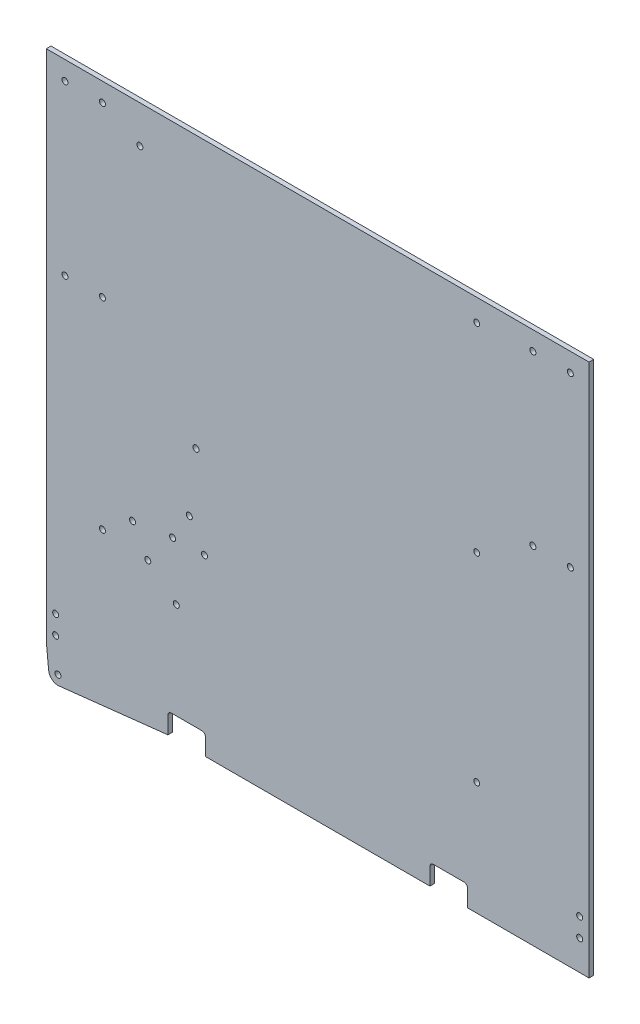
SolidWorks part; units mm, degrees
ref_plane "Front Plane" through (0, 0, 0) normal (0, 0, 1) x (1, 0, 0)
ref_plane "Top Plane" through (0, 0, 0) normal (0, 1, 0) x (1, 0, 0)
ref_plane "Right Plane" through (0, 0, 0) normal (1, 0, 0) x (0, 0, -1)
sketch "Sketch1" plane through (0, 0, 0) normal (0, 0, 1) x (1, 0, 0)
  line L0 (82.55, -20.32) -> (82.55, -6.35)
  line L2 (0, 0) -> (0, 341.63)
  line L3 (0, 341.63) -> (368.3, 341.63)
  line L4 (368.3, -20.32) -> (368.3, 341.63)
  line L5 (82.55, -6.35) -> (107.95, -6.35)
  line L6 (107.95, -6.35) -> (107.95, -20.32)
  line L7 (107.95, -20.32) -> (260.35, -20.32)
  line L8 (260.35, -20.32) -> (260.35, -6.35)
  line L9 (260.35, -6.35) -> (285.75, -6.35)
  line L10 (285.75, -6.35) -> (285.75, -20.32)
  line L11 (285.75, -20.32) -> (368.3, -20.32)
  line L12 (361.95, 12.7) -> (368.3, 12.7) construction
  line L13 (0, 0) -> (6.35, 0) construction
  line L14 (0.0315, -6.9818) -> (1.619, -22.8568)
  line L15 (8.6391, -28.5361) -> (82.55, -20.32)
  line L16 (0, 0) -> (0, -6.35)
  line L17 (85.725, 97.155) -> (82.9754, 95.5675) construction
  line L18 (97.0634, 115.6163) -> (58.5686, 93.3913) construction
  line L19 (97.0634, 115.6163) -> (107.3822, 97.7437) construction
  line L20 (58.5686, 93.3913) -> (68.8873, 75.5187) construction
  line L21 (107.3822, 97.7437) -> (68.8873, 75.5187) construction
  line L22 (97.0634, 115.6163) -> (68.8873, 75.5187) construction
  line L23 (58.5686, 93.3913) -> (107.3822, 97.7437) construction
  line L24 (7.9375, -22.225) -> (88.2169, 59.1366) construction
  line L25 (292.1, 56.63) -> (292.1, 191.63) construction
  line L26 (292.1, 191.63) -> (292.1, 326.63) construction
  line L27 (355.6, 328.93) -> (330.2, 328.93) construction
  line L28 (330.2, 328.93) -> (330.2, 214.63) construction
  line L29 (330.2, 214.63) -> (355.6, 214.63) construction
  line L30 (355.6, 214.63) -> (355.6, 328.93) construction
  line L31 (184.15, 341.63) -> (184.15, 269.4703) construction
  line L32 (12.7, 328.93) -> (38.1, 328.93) construction
  line L33 (38.1, 328.93) -> (38.1, 214.63) construction
  line L34 (12.7, 214.63) -> (12.7, 328.93) construction
  line L35 (38.1, 214.63) -> (12.7, 214.63) construction
  circle A0 centre (6.35, 0) radius 2.032
  circle A1 centre (6.35, 12.7) radius 2.032
  circle A2 centre (361.95, 0) radius 2.032
  circle A3 centre (361.95, 12.7) radius 2.032
  arc A5 (1.619, -22.8568) -> (8.6391, -28.5361) centre (7.9375, -22.225) ccw
  circle A6 centre (7.9375, -22.225) radius 2.032
  arc A7 (0, -6.35) -> (0.0315, -6.9818) centre (6.35, -6.35) ccw
  circle A8 centre (38.1, 78.105) radius 2.032
  circle A9 centre (85.725, 97.155) radius 2.032
  circle A10 centre (58.5686, 93.3913) radius 2.032
  circle A11 centre (68.8873, 75.5187) radius 2.032
  circle A12 centre (107.3822, 97.7437) radius 2.032
  circle A13 centre (97.0634, 115.6163) radius 2.032
  circle A14 centre (88.2169, 59.1366) radius 2.032
  circle A15 centre (292.1, 56.63) radius 2
  circle A16 centre (292.1, 191.63) radius 2
  circle A17 centre (292.1, 326.63) radius 2
  circle A18 centre (63.5, 316.23) radius 2.032
  circle A19 centre (101.6, 157.48) radius 2.032
  circle A20 centre (355.6, 328.93) radius 2.032
  circle A21 centre (330.2, 328.93) radius 2.032
  circle A22 centre (355.6, 214.63) radius 2.032
  circle A23 centre (330.2, 214.63) radius 2.032
  circle A24 centre (12.7, 328.93) radius 2.032
  circle A25 centre (38.1, 328.93) radius 2.032
  circle A26 centre (12.7, 214.63) radius 2.032
  circle A27 centre (38.1, 214.63) radius 2.032
  dimension "D6" = 4.064
  dimension "D10" = 6.35
  dimension "D11" = 4.064
  dimension "D17" = 38.1
  dimension "D27" = 4
  dimension "D31" = 4.064
  dimension "D32" = 25.4
  dimension "D36" = 4.064
  dimension "D2" = 361.95
  dimension "D3" = 13.97
  dimension "D4" = 25.4
  dimension "D5" = 152.4
  dimension "D7" = 12.7
  dimension "D8" = 6.35
  dimension "D9" = 20.32
  dimension "D12" = 22.225
  dimension "D13" = 1.5875
  dimension "D14" = 82.55
  dimension "D15" = 368.3
  dimension "D16" = 6.35
  dimension "D18" = 98.425
  dimension "D19" = 47.625
  dimension "D20" = 19.05
  dimension "D21" = 3.175
  dimension "D22" = 60
  dimension "D23" = 20.6375
  dimension "D24" = 44.45
  dimension "D25" = 38.1
  dimension "D26" = 114.3
  dimension "D28" = 135
  dimension "D29" = 15
  dimension "D30" = 76.2
  dimension "D33" = 63.5
  dimension "D34" = 184.15
  dimension "D35" = 101.6
  dimension "D37" = 114.3
  dimension "D38" = 25.4
  dimension "D39" = 12.7
  dimension "D40" = 12.7
extrude "Boss-Extrude1" add sketch "Sketch1" along normal blind 3.175
fillet "Fillet1" radius 2.286 4 edges at (285.75, -6.35, 1.5875) (107.95, -6.35, 1.5875) (260.35, -6.35, 1.5875) (82.55, -6.35, 1.5875)
